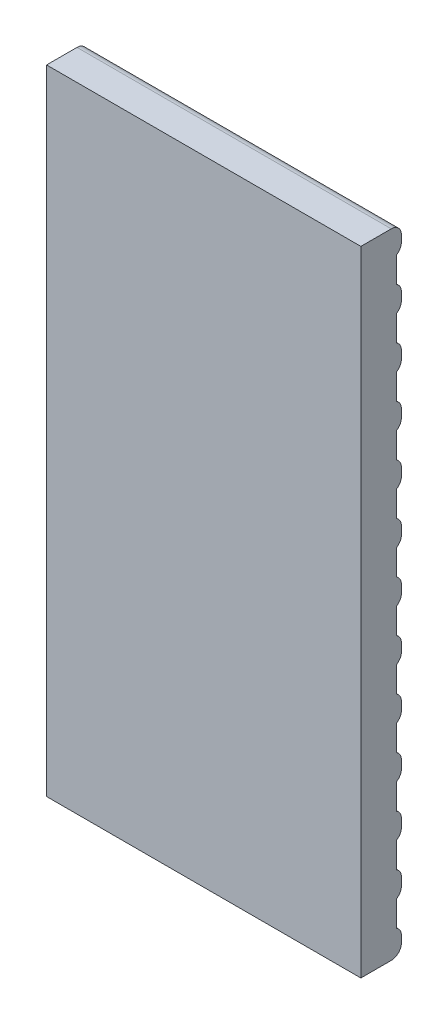
SolidWorks part; units mm, degrees
ref_plane "Front Plane" through (0, 0, 0) normal (0, 0, 1) x (1, 0, 0)
ref_plane "Top Plane" through (0, 0, 0) normal (0, 1, 0) x (1, 0, 0)
ref_plane "Right Plane" through (0, 0, 0) normal (1, 0, 0) x (0, 0, -1)
sketch "Sketch1" plane through (0, 0, 0) normal (0, 0, 1) x (1, 0, 0)
  line L1 (-7.874, 15.875) -> (7.874, 15.875)
  line L2 (-7.874, 15.875) -> (-7.874, -15.875)
  line L3 (-7.874, -15.875) -> (7.874, -15.875)
  line L4 (7.874, 15.875) -> (7.874, -15.875)
  line L5 (-7.874, 15.875) -> (7.874, -15.875) construction
  line L6 (-7.874, -15.875) -> (7.874, 15.875) construction
  point P0 (0, 0)
  dimension "D1" = 31.75
  dimension "D2" = 15.748
extrude "Boss-Extrude1" add sketch "Sketch1" along normal blind 1.778
sketch "Sketch2" plane through (0, 0, 0) normal (0, 0, -1) x (-1, 0, 0)
  line L0 (7.874, 15.875) -> (7.874, -15.875) construction
  line L1 (-7.874, -15.875) -> (7.874, -15.875)
  line L2 (-7.874, -15.875) -> (-7.874, -14.605)
  line L3 (-7.874, -14.605) -> (7.874, -14.605)
  line L4 (7.874, -15.875) -> (7.874, -14.605)
  line L5 (-7.874, -13.335) -> (-7.874, -12.065)
  line L6 (-7.874, -13.335) -> (7.874, -13.335)
  line L7 (7.874, -13.335) -> (7.874, -12.065)
  line L8 (-7.874, -12.065) -> (7.874, -12.065)
  line L9 (-7.874, -10.795) -> (-7.874, -9.525)
  line L10 (-7.874, -10.795) -> (7.874, -10.795)
  line L11 (7.874, -10.795) -> (7.874, -9.525)
  line L12 (-7.874, -9.525) -> (7.874, -9.525)
  line L13 (-7.874, -8.255) -> (-7.874, -6.985)
  line L14 (-7.874, -8.255) -> (7.874, -8.255)
  line L15 (7.874, -8.255) -> (7.874, -6.985)
  line L16 (-7.874, -6.985) -> (7.874, -6.985)
  line L17 (-7.874, -5.715) -> (-7.874, -4.445)
  line L18 (-7.874, -5.715) -> (7.874, -5.715)
  line L19 (7.874, -5.715) -> (7.874, -4.445)
  line L20 (-7.874, -4.445) -> (7.874, -4.445)
  line L21 (-7.874, -3.175) -> (-7.874, -1.905)
  line L22 (-7.874, -3.175) -> (7.874, -3.175)
  line L23 (7.874, -3.175) -> (7.874, -1.905)
  line L24 (-7.874, -1.905) -> (7.874, -1.905)
  line L25 (-7.874, -0.635) -> (-7.874, 0.635)
  line L26 (-7.874, -0.635) -> (7.874, -0.635)
  line L27 (7.874, -0.635) -> (7.874, 0.635)
  line L28 (-7.874, 0.635) -> (7.874, 0.635)
  line L29 (-7.874, 1.905) -> (-7.874, 3.175)
  line L30 (-7.874, 1.905) -> (7.874, 1.905)
  line L31 (7.874, 1.905) -> (7.874, 3.175)
  line L32 (-7.874, 3.175) -> (7.874, 3.175)
  line L33 (-7.874, 4.445) -> (-7.874, 5.715)
  line L34 (-7.874, 4.445) -> (7.874, 4.445)
  line L35 (7.874, 4.445) -> (7.874, 5.715)
  line L36 (-7.874, 5.715) -> (7.874, 5.715)
  line L37 (-7.874, 6.985) -> (-7.874, 8.255)
  line L38 (-7.874, 6.985) -> (7.874, 6.985)
  line L39 (7.874, 6.985) -> (7.874, 8.255)
  line L40 (-7.874, 8.255) -> (7.874, 8.255)
  line L41 (-7.874, 9.525) -> (-7.874, 10.795)
  line L42 (-7.874, 9.525) -> (7.874, 9.525)
  line L43 (7.874, 9.525) -> (7.874, 10.795)
  line L44 (-7.874, 10.795) -> (7.874, 10.795)
  line L45 (-7.874, 12.065) -> (-7.874, 13.335)
  line L46 (-7.874, 12.065) -> (7.874, 12.065)
  line L47 (7.874, 12.065) -> (7.874, 13.335)
  line L48 (-7.874, 13.335) -> (7.874, 13.335)
  line L49 (-7.874, 14.605) -> (-7.874, 15.875)
  line L50 (-7.874, 14.605) -> (7.874, 14.605)
  line L51 (7.874, 14.605) -> (7.874, 15.875)
  line L52 (-7.874, 15.875) -> (7.874, 15.875)
  dimension "D1" = 1.27
  dimension "D2" = 13
extrude "Boss-Extrude2" add sketch "Sketch2" along normal blind 0.254
fillet "Fillet1" radius 0.508 26 edges at (0, 15.875, -0.254) (0, 14.605, -0.254) (0, 13.335, -0.254) (0, 12.065, -0.254) (0, 10.795, -0.254) (0, 9.525, -0.254) (0, 8.255, -0.254) (0, 6.985, -0.254) (0, 5.715, -0.254) (0, 4.445, -0.254) (0, 3.175, -0.254) (0, 1.905, -0.254) (0, 0.635, -0.254) (0, -0.635, -0.254) (0, -1.905, -0.254) (0, -3.175, -0.254) (0, -4.445, -0.254) (0, -5.715, -0.254) (0, -6.985, -0.254) (0, -8.255, -0.254) (0, -9.525, -0.254) (0, -10.795, -0.254) (0, -15.875, -0.254) (0, -14.605, -0.254) (0, -12.065, -0.254) (0, -13.335, -0.254)
